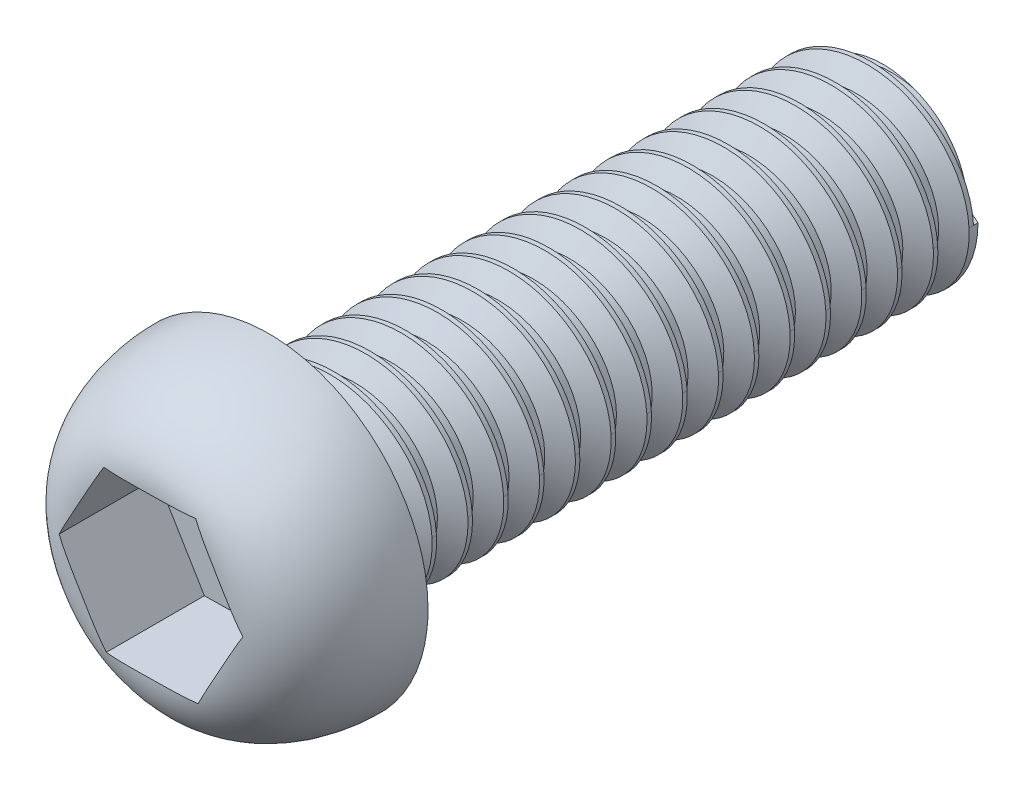
SolidWorks part; units mm, degrees
ref_plane "Front Plane" through (0, 0, 0) normal (0, 0, 1) x (1, 0, 0)
ref_plane "Top Plane" through (0, 0, 0) normal (0, 1, 0) x (1, 0, 0)
ref_plane "Right Plane" through (0, 0, 0) normal (1, 0, 0) x (0, 0, -1)
sketch "Sketch1" plane through (0, 0, 0) normal (0, 0, 1) x (1, 0, 0)
  circle A0 centre (0, 0) radius 1.25
  dimension "D1" = 2.5
extrude "Boss-Extrude1" add sketch "Sketch1" along normal blind 8
sketch "Sketch2" plane through (0, 0, 8) normal (0, 0, 1) x (1, 0, 0)
  circle A0 centre (0, 0) radius 2
  dimension "D1" = 4
extrude "Boss-Extrude2" add sketch "Sketch2" along normal blind 1.5
fillet "Fillet1" radius 1.5 1 edges at (2, 0, 9.5) second distance 1 first distance on face at (2, 0, 9.5)
sketch "Sketch3" plane through (0, 0, 9.5) normal (0, 0, 1) x (1, 0, 0)
  line L1 (1.1546, 0.0181) -> (0.5616, 1.0089)
  line L2 (0.5616, 1.0089) -> (-0.593, 0.9908)
  line L3 (-0.593, 0.9908) -> (-1.1546, -0.0181)
  line L4 (-1.1546, -0.0181) -> (-0.5616, -1.0089)
  line L5 (-0.5616, -1.0089) -> (0.593, -0.9908)
  line L6 (0.593, -0.9908) -> (1.1546, 0.0181)
  circle A0 centre (0, 0) radius 1 construction
  dimension "D1" = 2
extrude "Cut-Extrude1" cut sketch "Sketch3" against normal blind 1.25
thread "Thread2" pitch 0.45 method cut profile "Thread Profile1" start angle 0, offset 0, length 7.6, pitch 0.45, diameter 2.5
ref_plane "Plane4" through (1.25, 0, 0) normal (0, -1, 0) x (1, 0, 0)
sketch "Thread Profile1" plane through (1.25, 0, 0) normal (0, -1, 0) x (1, 0, 0)
  line L0 (0, 0) -> (0, 0.45) construction
  line L11 (0, 0) -> (0, 0.3937)
  line L12 (0, 0.3937) -> (-0.2436, 0.2531)
  line L13 (-0.2436, 0.2531) -> (-0.2436, 0.1406)
  line L15 (-0.2436, 0.1406) -> (0, 0)
  line L17 (-0.2436, 0.1969) -> (0, 0.1969) construction
  point P2 (0, 0)
  dimension "Pitch" = 0.45
  dimension "Profile_Angle" = 60
  dimension "Profile_Land" = 0.1125
  dimension "Profile_Height" = 0.2436
sketch "Sketch11" plane through (0, 0, 0) normal (0, 1, 0) x (1, 0, 0)
  line L0 (-0.497, 0) -> (-1.3657, -0.3892)
  line L1 (1.25, 0) -> (-1.25, 0) construction
  line L2 (-1.3657, -0.3892) -> (-1.4576, 0.1872)
  line L3 (-1.4576, 0.1872) -> (-0.497, 0.1872)
  line L4 (-0.497, 0.1872) -> (-0.497, 0)
ref_axis "Axis1" through (0, 0, 8) along (0, 0, -1)
revolve "Cut-Revolve1" cut sketch "Sketch11" angle 360 about axis through (0, 0, 8) along (0, 0, -1)
